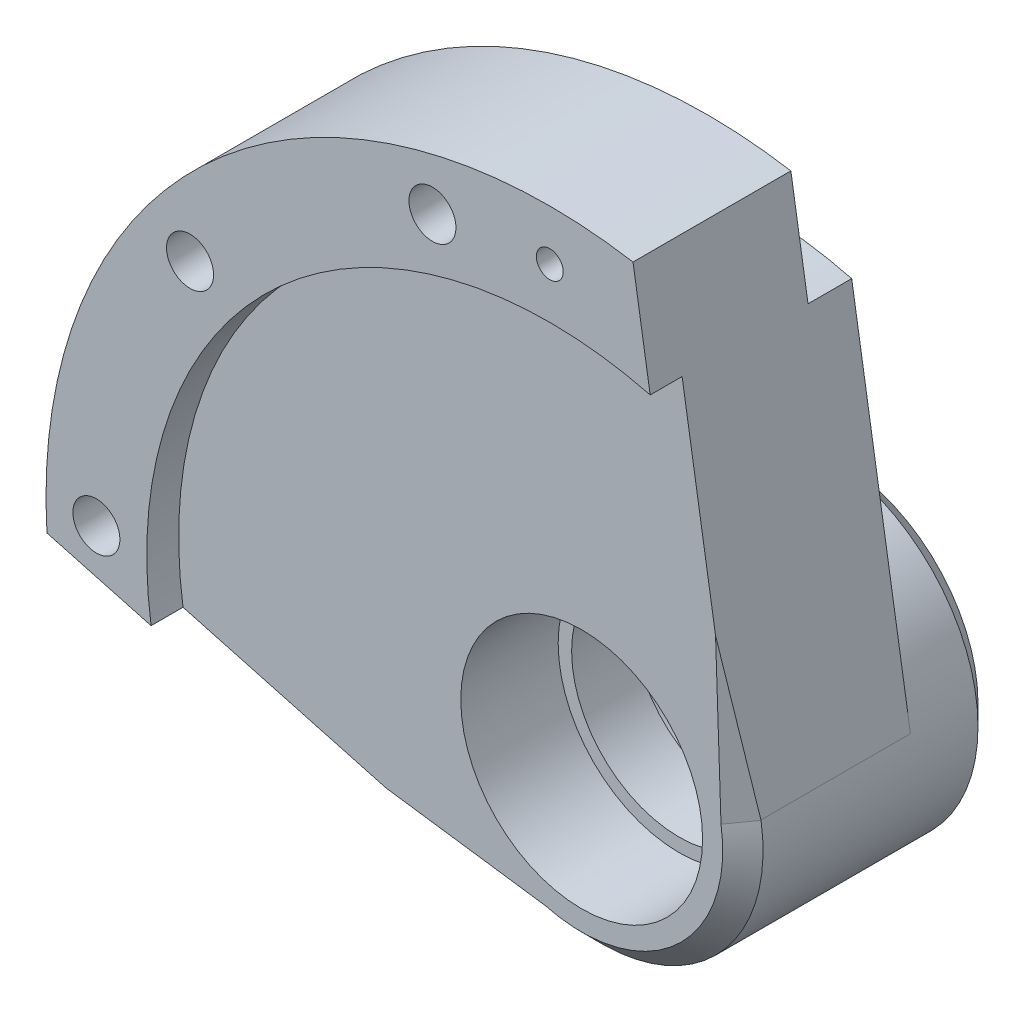
SolidWorks part; units mm, degrees
material "1.0503 (C45)"
ref_plane "Piano frontale" through (0, 0, 0) normal (0, 0, 1) x (1, 0, 0)
ref_plane "Piano superiore" through (0, 0, 0) normal (0, 1, 0) x (1, 0, 0)
ref_plane "Piano destro" through (0, 0, 0) normal (1, 0, 0) x (0, 0, -1)
sketch "Schizzo1" plane through (0, 0, 0) normal (0, 0, 1) x (1, 0, 0)
  line L0 (-1000, 0) -> (49000, 0) construction
  line L1 (0, -1000) -> (0, 49000) construction
  circle A0 centre (0, 0) radius 150
  circle A1 centre (0, 0) radius 32
  dimension "D1" = 300
  dimension "D2" = 64
extrude "Estrusione1" add sketch "Schizzo1" along normal blind 80.5
sketch "Schizzo2" plane through (0, 0, 80.5) normal (0, 0, 1) x (1, 0, 0)
  circle A0 centre (0, 0) radius 120
  dimension "D1" = 240
extrude "Estrusione2" cut sketch "Schizzo2" against normal blind 4.5
sketch "Schizzo3" plane through (0, 0, 76) normal (0, 0, 1) x (1, 0, 0)
  circle A0 centre (0, 0) radius 36
  dimension "D1" = 72
extrude "Estrusione3" cut sketch "Schizzo3" against normal blind 29
sketch "Schizzo4" plane through (0, 0, 0) normal (0, 0, -1) x (-1, 0, 0)
  circle A0 centre (0, 0) radius 36
  dimension "D1" = 72
extrude "Estrusione4" cut sketch "Schizzo4" against normal blind 29
sketch "Schizzo5" plane through (0, 0, 0) normal (0, 0, -1) x (-1, 0, 0)
  circle A0 centre (0, 0) radius 120
  dimension "D1" = 240
extrude "Estrusione5" cut sketch "Schizzo5" against normal blind 38.5 flip side to cut
sketch "Schizzo6" plane through (0, 0, 0) normal (0, 0, -1) x (-1, 0, 0)
  circle A0 centre (0, 0) radius 48
extrude "Estrusione6" cut sketch "Schizzo6" against normal blind 25.5 flip side to cut
sketch "Schizzo7" plane through (0, 0, 25.5) normal (0, 0, -1) x (-1, 0, 0)
  line L0 (0, -1000) -> (0, 49000) construction
  circle A0 centre (0, 135) radius 4
  dimension "D1" = 8
  dimension "D2" = 135
extrude "Estrusione7" cut sketch "Schizzo7" against normal through all
sketch "Schizzo8" plane through (0, 0, 38.5) normal (0, 0, -1) x (-1, 0, 0)
  line L0 (0, 0) -> (173.7202, 0) construction
  circle A0 centre (135, 0) radius 7
  dimension "D1" = 14
  dimension "D2" = 135
extrude "Estrusione8" cut sketch "Schizzo8" against normal through all
pattern_circular "RipetizioneCircolare1" count 3 over 75 about axis through (0, 0, 38.5) along (0, 0, -1) of "Estrusione8"
sketch "Schizzo9" plane through (0, 0, 25.5) normal (0, 0, -1) x (-1, 0, 0)
  line L0 (0, 0) -> (0, 160.0568) construction
  line L1 (0, 0) -> (179.9663, 0) construction
  line L2 (0, 0) -> (169.4369, -10.3929) construction
  line L3 (0, 0) -> (-26.6901, 159.3227) construction
  line L4 (-24.783, 147.9385) -> (-47.3888, 7.6354)
  line L5 (149.7186, -9.1834) -> (12.547, -46.3311)
  arc A0 (149.7186, -9.1834) -> (-24.783, 147.9385) centre (0, 0) ccw
  circle A1 centre (0, 0) radius 150 construction
  arc A3 (-47.3888, 7.6354) -> (12.547, -46.3311) centre (0, 0) ccw
  dimension "D3" = 48
  dimension "D1" = 3.51
  dimension "D2" = 170.49
extrude "Estrusione9" cut sketch "Schizzo9" against normal through all flip side to cut
chamfer "Smusso1" distance 6 angle 45 1 edges at (-48, 0, 0)
sketch "Schizzo10" plane through (0, 0, 0) normal (1, 0, 0) x (0, 0, -1)
  line L0 (-76, -42) -> (-70, -48)
  line L1 (-76, 7.6354) -> (-76, -48) construction
  line L2 (-76, -48) -> (-6, -48) construction
  line L3 (-70, -48) -> (-76, -48)
  line L4 (-76, -48) -> (-76, -42)
  dimension "D1" = 6
  dimension "D2" = 6
revolve "Taglia-Rivoluzione1" cut sketch "Schizzo10" angle 15 about axis through (0, 0, 80.5) along (0, 0, -1) other way angle 99
ref_plane "Piano3" through (-0.6906, 7.2254, 0.4482) normal (-0.095, 0.9936, 0.0616) x (-0.9955, -0.0948, -0.0062)
ref_plane "Piano4" through (-7.1136, 1.4421, 0.4482) normal (0.9782, -0.1983, -0.0616) x (-0.0662, -0.0163, -0.9977)
sketch "Schizzo12" plane through (-0.6906, 7.2254, 0.4482) normal (-0.095, 0.9936, 0.0616) x (-0.9955, -0.0948, -0.0062)
  line L0 (-42.3867, 75.4353) -> (-48.338, 69.387)
  line L1 (-48.338, 69.387) -> (-48.8696, 76.1812)
  line L2 (-48.8696, 76.1812) -> (-42.3867, 75.4353)
extrude "Estrusione10" cut sketch "Schizzo12" along normal through all
sketch "Schizzo13" plane through (-7.1136, 1.4421, 0.4482) normal (0.9782, -0.1983, -0.0616) x (-0.0662, -0.0163, -0.9977)
  line L0 (-74.4407, -44.1101) -> (-68.2571, -49.9208)
  line L1 (-68.2571, -49.9208) -> (-76.4634, -52.4582)
  line L2 (-76.4634, -52.4582) -> (-74.4407, -44.1101)
extrude "Estrusione11" cut sketch "Schizzo13" against normal through all
sketch "Schizzo14" plane through (0, 0, 80.5) normal (0, 0, 1) x (1, 0, 0)
  line L0 (24.783, 147.9385) -> (29.894, 116.2168)
  line L1 (-149.7186, -9.1834) -> (-118.7049, -17.5823)
  arc A0 (24.783, 147.9385) -> (-149.7186, -9.1834) centre (0, 0) ccw
  arc A1 (29.894, 116.2168) -> (-118.7049, -17.5823) centre (0, 0) ccw
  circle A2 centre (-135, 0) radius 7
  circle A3 centre (-107.1027, 82.1828) radius 7
  circle A4 centre (-34.9406, 130.4) radius 7
  circle A5 centre (0, 135) radius 4
  dimension "D1" = 8
  dimension "D2" = 14
extrude "Estrusione12" add sketch "Schizzo14" along normal blind 5
ref_plane "Piano5" through (0, 0, 38) normal (0, 0, 1) x (1, 0, 0)
